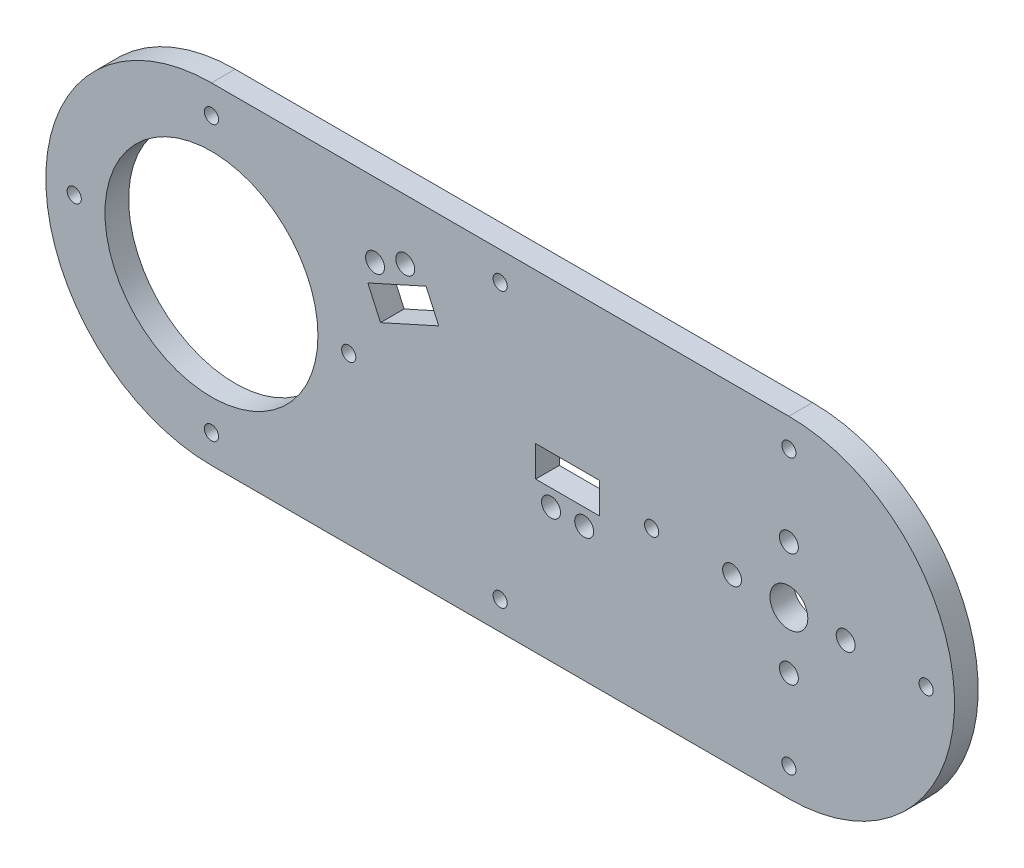
SolidWorks part; units mm, degrees
ref_plane "Front Plane" through (0, 0, 0) normal (0, 0, 1) x (1, 0, 0)
ref_plane "Top Plane" through (0, 0, 0) normal (0, 1, 0) x (1, 0, 0)
ref_plane "Right Plane" through (0, 0, 0) normal (1, 0, 0) x (0, 0, -1)
sketch "Sketch1" plane through (0, 0, 0) normal (0, 0, 1) x (1, 0, 0)
  line L0 (61, 0) -> (-61, 0) construction
  line L1 (-23.2463, 20.8784) -> (-21.8066, 17.6883) construction
  line L2 (61, -35) -> (-61, -35)
  line L3 (61, 35) -> (-61, 35)
  line L17 (7.5, 3.25) -> (7.5, -3.25)
  line L20 (7.5, -3.25) -> (21, -3.25)
  line L23 (21, -3.25) -> (21, 3.25)
  line L24 (21, 3.25) -> (7.5, 3.25)
  line L37 (-61, 0) -> (-27.959, 14.9116) construction
  line L38 (-27.959, 14.9116) -> (-25.2852, 8.987)
  line L39 (-25.2852, 8.987) -> (-12.9803, 14.5403)
  line L40 (-12.9803, 14.5403) -> (-15.6541, 20.4649)
  line L41 (-15.6541, 20.4649) -> (-27.959, 14.9116)
  arc A0 (61, -35) -> (61, 35) centre (61, 0) ccw
  arc A1 (-61, 35) -> (-61, -35) centre (-61, 0) ccw
  circle A2 centre (61, 0) radius 4
  circle A3 centre (-61, 0) radius 22.5
  circle A4 centre (-61, -29) radius 1.5
  circle A5 centre (-61, 29) radius 1.5
  circle A6 centre (61, 29) radius 1.5
  circle A7 centre (61, -29) radius 1.5
  circle A9 centre (0, 29) radius 1.5
  circle A12 centre (-90, 0) radius 1.5
  circle A13 centre (-32, 0) radius 1.5
  circle A16 centre (90, 0) radius 1.5
  circle A17 centre (32, 0) radius 1.5
  circle A34 centre (61, 12) radius 2
  circle A35 centre (61, -12) radius 2
  circle A36 centre (49, 0) radius 2
  circle A37 centre (73, 0) radius 2
  circle A44 centre (10.75, -6.75) radius 2
  circle A45 centre (17.75, -6.75) radius 2
  circle A46 centre (-20.0562, 22.3182) radius 2
  circle A47 centre (-26.4365, 19.4387) radius 2
  circle A48 centre (0, -29) radius 1.5
  point P5 (0, 0)
  point P27 (-61, 0)
  point P28 (7.5, 0)
  point P32 (-61, 0)
  point P74 (14.25, -6.75)
  point P83 (-23.2463, 20.8784)
  dimension "D1" = 8
  dimension "D3" = 6
  dimension "D4" = 3
  dimension "D5" = 6
  dimension "D6" = 3
  dimension "D8" = 3
  dimension "D9" = 3
  dimension "D12" = 3
  dimension "D13" = 6
  dimension "D14" = 70
  dimension "D15" = 12
  dimension "D16" = 12
  dimension "D19" = 3
  dimension "D20" = 3
  dimension "D24" = 29
  dimension "D25" = 3
  dimension "D26" = 3
  dimension "D27" = 4
  dimension "D28" = 4
  dimension "D29" = 4
  dimension "D30" = 29
  dimension "D31" = 13.5
  dimension "D32" = 6.5
  dimension "D33" = 68.5
  dimension "D34" = 3
  dimension "D45" = 45
  dimension "D22" = 4
  dimension "D41" = 4
  dimension "D42" = 4
  dimension "D7" = 122
  dimension "D10" = 6
  dimension "D11" = 6
  dimension "D17" = 12
  dimension "D18" = 58
  dimension "D21" = 12
  dimension "D23" = 29
  dimension "D35" = 6
  dimension "D36" = 13.5
  dimension "D37" = 6.5
  dimension "D38" = 7
  dimension "D39" = 3.5
  dimension "D40" = 3.5
  dimension "D43" = 7
  dimension "D44" = 36.25
extrude "Boss-Extrude1" add sketch "Sketch1" along normal blind 5
